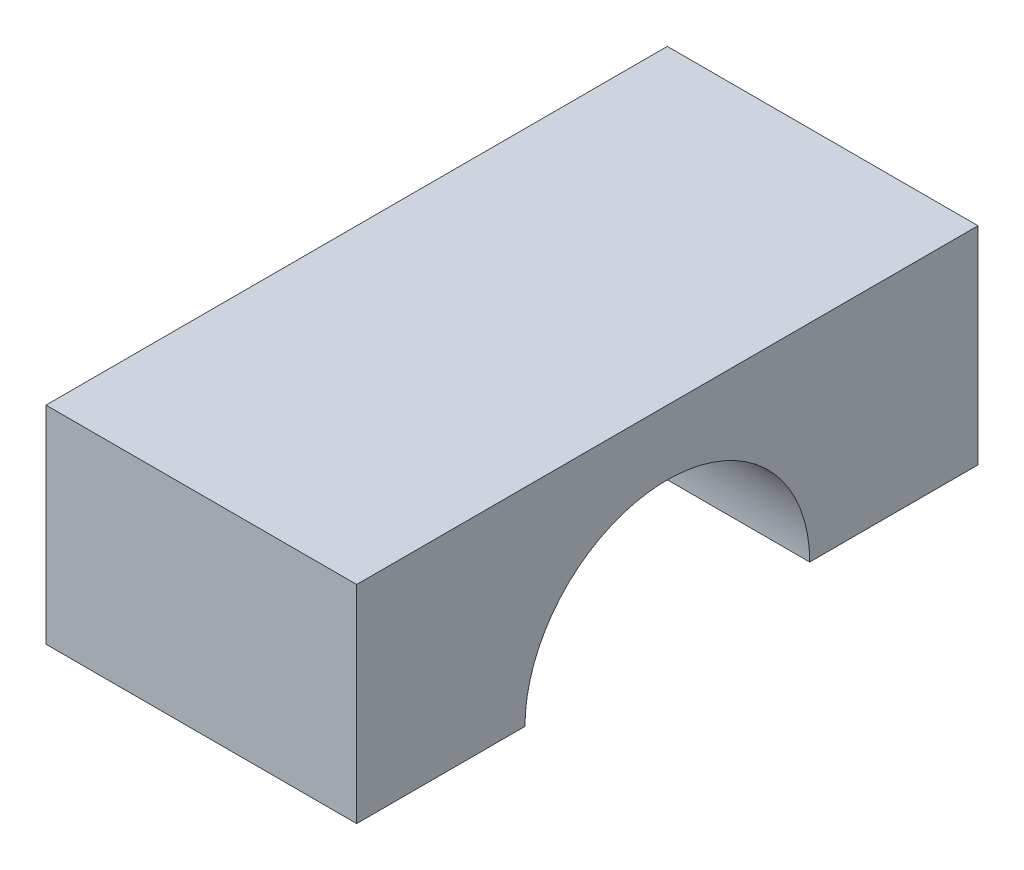
SolidWorks part; units mm, degrees
ref_plane "Front Plane" through (0, 0, 0) normal (0, 0, 1) x (1, 0, 0)
ref_plane "Top Plane" through (0, 0, 0) normal (0, 1, 0) x (1, 0, 0)
ref_plane "Right Plane" through (0, 0, 0) normal (1, 0, 0) x (0, 0, -1)
sketch "Sketch1" plane through (0, 0, 0) normal (1, 0, 0) x (0, 0, -1)
  line L1 (0, 0) -> (76.2, 0)
  line L2 (0, 0) -> (0, 25.4)
  line L3 (0, 25.4) -> (76.2, 25.4)
  line L4 (76.2, 0) -> (76.2, 25.4)
  dimension "D1" = 76.2
  dimension "D2" = 25.4
extrude "Boss-Extrude1" add sketch "Sketch1" along normal blind 38.1
sketch "Sketch2" plane through (38.1, 0, 0) normal (1, 0, 0) x (0, 0, -1)
  line L0 (0, 0) -> (76.2, 0) construction
  circle A0 centre (38.1, 0) radius 17.4625
  dimension "D1" = 34.925
extrude "Cut-Extrude1" cut sketch "Sketch2" against normal through all
